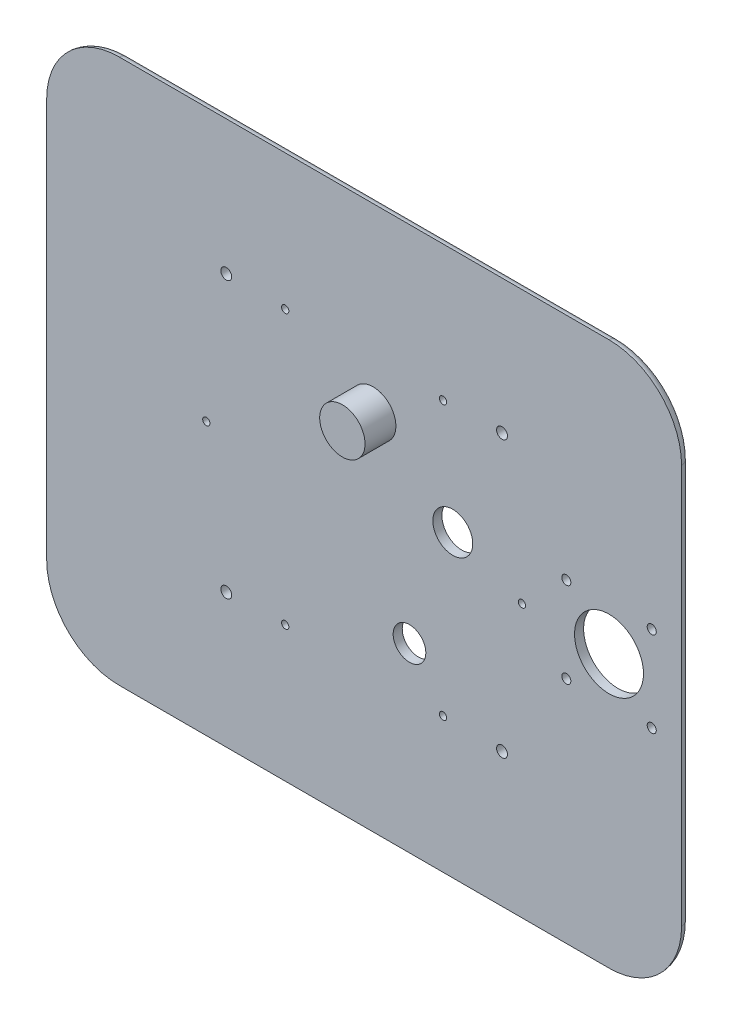
SolidWorks part; units mm, degrees
ref_plane "Front Plane" through (0, 0, 0) normal (0, 0, 1) x (1, 0, 0)
ref_plane "Top Plane" through (0, 0, 0) normal (0, 1, 0) x (1, 0, 0)
ref_plane "Right Plane" through (0, 0, 0) normal (1, 0, 0) x (0, 0, -1)
sketch "Sketch1" plane through (0, 0, 0) normal (0, 0, 1) x (1, 0, 0)
  line L0 (0, 87) -> (0, 0) construction
  line L1 (-175, 150) -> (175, 150)
  line L2 (-175, 150) -> (-175, -150)
  line L3 (-175, -150) -> (175, -150)
  line L4 (175, 150) -> (175, -150)
  line L5 (-175, 150) -> (175, -150) construction
  line L6 (-175, -150) -> (175, 150) construction
  line L7 (-43.5, 75.3442) -> (0, 0) construction
  line L8 (-76.013, -76.015) -> (76.013, 76.015) construction
  line L9 (-76.013, 76.015) -> (76.013, -76.015) construction
  line L12 (111.45, -23.55) -> (158.55, -23.55) construction
  line L13 (111.45, -23.55) -> (111.45, 23.55) construction
  line L14 (111.45, 23.55) -> (158.55, 23.55) construction
  line L15 (158.55, -23.55) -> (158.55, 23.55) construction
  line L16 (111.45, -23.55) -> (158.55, 23.55) construction
  line L17 (111.45, 23.55) -> (158.55, -23.55) construction
  circle A0 centre (0, 0) radius 87 construction
  circle A1 centre (-43.5, 75.3442) radius 2
  circle A2 centre (43.5, 75.3442) radius 2
  circle A3 centre (87, 0) radius 2
  circle A4 centre (43.5, -75.3442) radius 2
  circle A5 centre (-43.5, -75.3442) radius 2
  circle A6 centre (-87, 0) radius 2
  circle A13 centre (-76.013, -76.015) radius 3
  circle A14 centre (76.013, 76.015) radius 3
  circle A15 centre (76.013, -76.015) radius 3
  circle A16 centre (0, 0) radius 107.5 construction
  circle A17 centre (-76.013, 76.015) radius 3
  circle A18 centre (135, 0) radius 19
  circle A19 centre (158.55, -23.55) radius 2.5
  circle A20 centre (111.45, -23.55) radius 2.5
  circle A21 centre (111.45, 23.55) radius 2.5
  circle A22 centre (158.55, 23.55) radius 2.5
  point P0 (0, 0)
  point P23 (0, 0)
  point P39 (0, 0)
  point P48 (135, 0)
  dimension "D3" = 174
  dimension "D4" = 4
  dimension "D6" = 215
  dimension "D10" = 5
  dimension "D12" = 6
  dimension "D13" = 6
  dimension "D8" = 38
  dimension "D9" = 135
  dimension "D1" = 300
  dimension "D2" = 350
  dimension "D5" = 30
  dimension "D7" = 152.03
  dimension "D11" = 47.1
  dimension "D14" = 4
extrude "Boss-Extrude1" add sketch "Sketch1" along normal blind 5
sketch "Sketch2" plane through (0, 0, 0) normal (0, 0, -1) x (-1, 0, 0)
  line L0 (-175, -150) -> (-175, 150) construction
  line L1 (175, -150) -> (-175, -150) construction
  line L2 (-175, 150) -> (175, 150) construction
  line L3 (-175, -150) -> (-175, 150) construction
  line L4 (-175, 150) -> (175, 150) construction
  circle A0 centre (-48.87, 15) radius 11
  circle A1 centre (-25, -50) radius 9
  circle A2 centre (-5, 50) radius 10
  dimension "D2" = 22
  dimension "D3" = 126.13
  dimension "D4" = 18
  dimension "D7" = 20
  dimension "D1" = 135
  dimension "D5" = 100
  dimension "D6" = 150
  dimension "D8" = 100
  dimension "D9" = 170
extrude "Cut-Extrude1" cut sketch "Sketch2" against normal up to next
fillet "Fillet1" radius 40 4 edges at (175, 150, 2.5) (-175, 150, 2.5) (-175, -150, 2.5) (175, -150, 2.5)
fillet "Fillet2" radius 5 8 edges at (163.2843, 138.2843, 0) (175, 0, 0) (163.2843, -138.2843, 0) (0, -150, 0) (-163.2843, -138.2843, 0) (-175, 0, 0) (-163.2843, 138.2843, 0) (0, 150, 0)
sketch "Sketch3" plane through (0, 0, 5) normal (0, 0, 1) x (1, 0, 0)
  circle A0 centre (5, 50) radius 10
  circle A1 centre (5, 50) radius 12.5
  dimension "D1" = 25
extrude "Boss-Extrude2" add sketch "Sketch3" along normal blind 15
sketch "Sketch4" plane through (0, 0, 20) normal (0, 0, 1) x (1, 0, 0)
  circle A0 centre (5, 50) radius 12.5
extrude "Boss-Extrude3" add sketch "Sketch4" along normal blind 2
